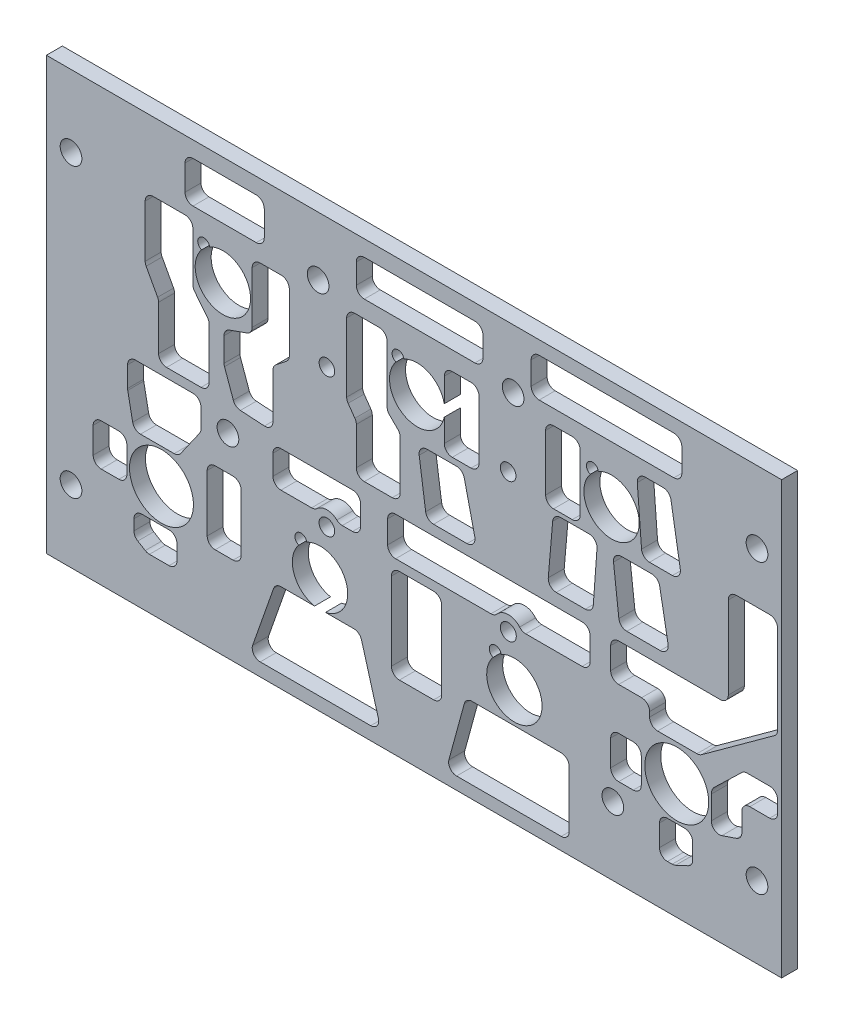
SolidWorks part; units mm, degrees
ref_plane "Front Plane" through (0, 0, 0) normal (0, 0, 1) x (1, 0, 0)
ref_plane "Top Plane" through (0, 0, 0) normal (0, 1, 0) x (1, 0, 0)
ref_plane "Right Plane" through (0, 0, 0) normal (1, 0, 0) x (0, 0, -1)
sketch "Sketch1" plane through (0, 0, 0) normal (0, 0, 1) x (1, 0, 0)
  line L4 (0, 85.725) -> (-146.05, 85.725)
  line L5 (-146.05, 85.725) -> (-146.05, 0)
  line L6 (-146.05, 0) -> (0, 0)
  line L7 (0, 0) -> (0, 85.725)
  line L8 (0, 85.725) -> (-146.05, 85.725)
  line L9 (-146.05, 85.725) -> (-146.05, 0)
  line L10 (-146.05, 0) -> (0, 0)
  line L11 (0, 0) -> (0, 85.725)
  dimension "D1" = 0
extrude "Backplate Body" add sketch "Sketch1" against normal blind 3.175
hole_wizard "#6 Clearance Hole1" positions "Sketch3" profile "Sketch2" hole size "#6" standard "ANSI Inch"
sketch "Sketch3" plane through (0, 0, -3.175) normal (0, 0, -1) x (-1, 0, 0)
  point P0 (4.8895, 71.4375)
  point P3 (53.34, 74.041)
  point P6 (92.075, 74.041)
  point P9 (141.1605, 71.4375)
  point P12 (109.982, 38.735)
  point P15 (141.1605, 14.2875)
  point P18 (33.528, 13.589)
  point P21 (4.8895, 14.2875)
sketch "Sketch2" plane through (-4.8895, 71.4375, -3.175) normal (1, 0, 0) x (0, 1, 0)
  line L0 (0, 0) -> (0, 13.9934)
  line L1 (0, 13.9934) -> (2.1526, 12.7)
  line L2 (2.1526, 12.7) -> (2.1526, 0)
  line L5 (2.1526, 0) -> (0, 0)
  line L10 (0, 13.9934) -> (-2.1526, 12.7) construction
  line L11 (0, -6.35) -> (0, 107.95) construction
  dimension "Hole Dia." = 4.3053
  dimension "Hole Depth" = 12.7
  dimension "Drill Angle" = 118
sketch "Sketch4" plane through (0, 0, -3.175) normal (0, 0, -1) x (-1, 0, 0)
  circle A0 centre (20.828, 22.987) radius 6.35
  circle A1 centre (123.19, 22.987) radius 6.35
  arc A2 (36.4069, 68.9682) -> (38.001, 67.6635) centre (33.782, 64.135) ccw
  arc A3 (75.0149, 68.9682) -> (76.609, 67.6635) centre (72.39, 64.135) ccw
  arc A4 (113.6229, 68.9682) -> (115.217, 67.6635) centre (110.998, 64.135) ccw
  arc A5 (94.3189, 27.8202) -> (95.913, 26.5155) centre (91.694, 22.987) ccw
  arc A6 (55.7109, 27.8202) -> (57.305, 26.5155) centre (53.086, 22.987) ccw
  arc A7 (38.001, 67.6635) -> (36.4069, 68.9682) centre (37.5823, 68.778) ccw
  arc A8 (76.609, 67.6635) -> (75.0149, 68.9682) centre (76.1903, 68.778) ccw
  arc A9 (115.217, 67.6635) -> (113.6229, 68.9682) centre (114.7983, 68.778) ccw
  arc A10 (57.305, 26.5155) -> (55.7109, 27.8202) centre (56.8863, 27.63) ccw
  arc A11 (95.913, 26.5155) -> (94.3189, 27.8202) centre (95.4943, 27.63) ccw
  dimension "D1" = 12.7
  dimension "D2" = 11
  dimension "D3" = 2.3813
extrude "Switch Mount Holes" cut sketch "Sketch4" against normal through all
sketch "Sketch6" plane through (0, 0, -3.175) normal (0, 0, -1) x (-1, 0, 0)
  line L0 (0.7854, 59.7497) -> (0.7854, 42.2627)
  line L1 (1.4397, 40.9784) -> (15.8873, 30.4799)
  line L4 (16.8205, 30.1766) -> (24.6388, 30.1766)
  line L5 (26.2263, 31.7641) -> (26.2263, 32.7329)
  line L6 (27.8138, 34.3204) -> (32.3673, 34.3204)
  line L7 (33.9548, 35.9079) -> (33.9548, 40.2156)
  line L8 (32.3673, 41.8031) -> (12.1743, 41.8031)
  line L9 (10.5868, 43.3906) -> (10.5868, 59.7497)
  line L10 (8.9993, 61.3372) -> (2.3729, 61.3372)
  line L11 (21.4, 75.3506) -> (48.1668, 75.3506)
  line L12 (49.7543, 76.9381) -> (49.7543, 81.4624)
  line L13 (48.1668, 83.0499) -> (21.4, 83.0499)
  line L14 (19.8125, 81.4624) -> (19.8125, 76.9381)
  line L15 (59.3356, 80.9492) -> (59.3356, 76.9381)
  line L16 (60.9231, 75.3506) -> (82.8992, 75.3506)
  line L17 (84.4867, 76.9381) -> (84.4867, 80.9492)
  line L18 (82.8992, 82.5367) -> (60.9231, 82.5367)
  line L19 (28.672, 70.9074) -> (27.8272, 59.8641)
  line L20 (26.2443, 58.3977) -> (21.6898, 58.3977)
  line L21 (20.1244, 60.2489) -> (21.9848, 71.2922)
  line L22 (23.5503, 72.616) -> (27.0892, 72.616)
  line L23 (46.8767, 70.769) -> (46.8767, 59.6575)
  line L24 (45.2892, 58.07) -> (41.5893, 58.07)
  line L25 (40.0018, 59.6575) -> (40.0018, 70.769)
  line L26 (41.5893, 72.3565) -> (45.2892, 72.3565)
  line L27 (38.2576, 57.2789) -> (43.8996, 57.2789)
  line L28 (45.4813, 55.8276) -> (46.355, 45.6783)
  line L29 (44.7734, 43.9546) -> (38.997, 43.9546)
  line L30 (37.4137, 45.4268) -> (36.6743, 55.5761)
  line L31 (24.2194, 55.3227) -> (22.5486, 46.1448)
  line L32 (24.1104, 44.273) -> (30.7553, 44.273)
  line L33 (32.3322, 45.6779) -> (33.3948, 54.8558)
  line L34 (31.8178, 56.6259) -> (25.7812, 56.6259)
  line L35 (61.6963, 71.619) -> (65.4237, 71.619)
  line L36 (67.0112, 70.0315) -> (67.0112, 58.4598)
  line L37 (65.4237, 56.8723) -> (61.6963, 56.8723)
  line L38 (60.1088, 58.4598) -> (60.1088, 70.0315)
  line L39 (78.3684, 70.3657) -> (78.3684, 59.0552)
  line L40 (77.9034, 57.9327) -> (76.2306, 56.2599)
  line L41 (75.7657, 55.1374) -> (75.7657, 45.5421)
  line L42 (77.3532, 43.9546) -> (82.8992, 43.9546)
  line L43 (84.4867, 45.5421) -> (84.4867, 52.9982)
  line L44 (84.774, 53.9091) -> (86.1126, 55.8195)
  line L45 (86.3999, 56.7304) -> (86.3999, 70.3657)
  line L46 (84.8124, 71.9532) -> (79.9559, 71.9532)
  line L47 (64.5881, 55.7521) -> (70.4272, 55.7521)
  line L48 (71.9989, 53.9418) -> (70.7103, 44.8514)
  line L49 (69.1385, 43.4867) -> (62.4983, 43.4867)
  line L50 (60.9512, 45.4299) -> (63.041, 54.5203)
  line L51 (104.3617, 82.5367) -> (116.9306, 82.5367)
  line L52 (118.5181, 80.9492) -> (118.5181, 75.9239)
  line L53 (116.9306, 74.3364) -> (104.3617, 74.3364)
  line L54 (102.7742, 75.9239) -> (102.7742, 80.9492)
  line L55 (116.9515, 70.4508) -> (116.9515, 60.795)
  line L56 (116.6029, 59.8023) -> (114.0887, 56.6647)
  line L57 (113.7401, 55.6721) -> (113.7401, 45.5421)
  line L58 (115.3276, 43.9546) -> (122.1785, 43.9546)
  line L59 (123.766, 45.5421) -> (123.766, 54.3743)
  line L60 (123.9579, 55.131) -> (126.2372, 59.3351)
  line L61 (126.4292, 60.0918) -> (126.4292, 70.4508)
  line L62 (124.8417, 72.0383) -> (118.539, 72.0383)
  line L63 (105.1722, 69.6262) -> (105.1722, 59.351)
  line L64 (106.2241, 57.8565) -> (109.7117, 56.6066)
  line L65 (110.7636, 55.1122) -> (110.7636, 50.368)
  line L66 (110.6706, 49.8324) -> (108.9167, 44.9385)
  line L67 (107.5209, 43.8896) -> (102.7372, 43.5917)
  line L68 (101.051, 45.1761) -> (101.051, 54.0148)
  line L69 (100.4562, 55.2536) -> (98.3918, 56.9078)
  line L70 (97.797, 58.1467) -> (97.797, 69.6262)
  line L71 (99.3845, 71.2137) -> (103.5847, 71.2137)
  line L72 (39.6269, 33.7908) -> (50.842, 33.7908)
  line L73 (78.2665, 35.3783) -> (78.2665, 39.8664)
  line L74 (76.679, 41.4539) -> (39.6269, 41.4539)
  line L75 (38.0394, 39.8664) -> (38.0394, 35.3783)
  line L76 (83.642, 39.7608) -> (83.642, 35.7883)
  line L77 (85.2295, 34.2008) -> (87.2841, 34.2008)
  line L78 (101.051, 35.7883) -> (101.051, 39.7608)
  line L79 (99.4635, 41.3483) -> (85.2295, 41.3483)
  line L80 (115.3458, 40.5393) -> (115.3458, 36.8018)
  line L81 (115.6328, 35.8915) -> (119.3681, 30.5551)
  line L82 (120.6686, 29.8779) -> (127.3572, 29.8779)
  line L83 (128.9152, 31.1612) -> (129.8894, 36.1507)
  line L84 (129.9188, 36.4549) -> (129.9188, 40.5393)
  line L85 (128.3313, 42.1268) -> (116.9333, 42.1268)
  line L86 (0.7854, 30.2344) -> (0.7854, 27.9015)
  line L87 (2.3729, 26.314) -> (6.3156, 26.314)
  line L88 (7.9031, 24.7265) -> (7.9031, 21.0409)
  line L91 (13.9709, 20.0555) -> (13.9709, 24.6575)
  line L92 (13.3361, 26.1523) -> (7.9216, 31.3768)
  line L93 (6.8193, 31.8219) -> (2.3729, 31.8219)
  line L94 (18.5828, 10.0167) -> (21.0703, 8.8579)
  line L95 (21.7407, 8.7095) -> (22.6736, 8.7095)
  line L96 (24.2611, 10.297) -> (24.2611, 14.5475)
  line L97 (22.6736, 16.135) -> (19.2531, 16.135)
  line L98 (17.6656, 14.5475) -> (17.6656, 11.4558)
  line L99 (27.8819, 24.3095) -> (27.8819, 19.1834)
  line L100 (29.4694, 17.5959) -> (32.3673, 17.5959)
  line L101 (33.9548, 19.1834) -> (33.9548, 24.3095)
  line L102 (32.3673, 25.897) -> (29.4694, 25.897)
  line L103 (43.7793, 2.4684) -> (64.5682, 2.4684)
  line L104 (66.0995, 4.4745) -> (63.0373, 15.675)
  line L105 (61.506, 16.8438) -> (43.7793, 16.8438)
  line L106 (42.1918, 15.2563) -> (42.1918, 4.0559)
  line L107 (67.5359, 30.389) -> (67.5359, 14.8805)
  line L108 (69.1234, 13.293) -> (75.9295, 13.293)
  line L109 (77.517, 14.8805) -> (77.517, 30.389)
  line L110 (75.9295, 31.9765) -> (69.1234, 31.9765)
  line L111 (83.4506, 16.4411) -> (80.1004, 4.6154)
  line L112 (81.6278, 2.5952) -> (103.578, 2.5952)
  line L113 (105.0761, 4.708) -> (100.9298, 16.5336)
  line L114 (99.4317, 17.5959) -> (84.978, 17.5959)
  line L115 (114.1111, 30.2647) -> (114.1111, 18.9987)
  line L116 (112.5236, 17.4112) -> (108.9618, 17.4112)
  line L117 (107.3743, 18.9987) -> (107.3743, 30.2647)
  line L118 (108.9618, 31.8522) -> (112.5236, 31.8522)
  line L119 (130.0717, 26.6877) -> (130.0717, 21.5613)
  line L120 (131.6592, 19.9738) -> (135.1785, 19.9738)
  line L121 (136.766, 21.5613) -> (136.766, 26.6877)
  line L122 (135.1785, 28.2752) -> (131.6592, 28.2752)
  line L123 (121.6942, 16.2539) -> (127.0772, 16.2539)
  line L124 (128.6647, 14.6664) -> (128.6647, 12.5851)
  line L125 (127.9016, 11.2285) -> (126.4171, 10.3264)
  line L126 (125.5927, 10.0955) -> (121.6942, 10.0955)
  line L127 (120.1067, 11.683) -> (120.1067, 14.6664)
  line L129 (57.7397, 33.7908) -> (76.679, 33.7908)
  line L130 (93.3749, 34.2008) -> (99.4635, 34.2008)
  line L131 (8.9787, 19.5382) -> (11.8715, 18.5528)
  line L132 (0.0043, 85.727) -> (146.0543, 85.727) construction
  line L133 (0.0043, 85.727) -> (0.0043, 0.002) construction
  arc A0 (121.6942, 10.0955) -> (120.1067, 11.683) centre (121.6942, 11.683) cw
  arc A1 (126.4171, 10.3264) -> (125.5927, 10.0955) centre (125.5927, 11.683) cw
  arc A2 (128.6647, 12.5851) -> (127.9016, 11.2285) centre (127.0772, 12.5851) cw
  arc A3 (127.0772, 16.2539) -> (128.6647, 14.6664) centre (127.0772, 14.6664) cw
  arc A4 (136.766, 26.6877) -> (135.1785, 28.2752) centre (135.1785, 26.6877) ccw
  arc A5 (121.6942, 16.2539) -> (120.1067, 14.6664) centre (121.6942, 14.6664) ccw
  arc A6 (135.1785, 19.9738) -> (136.766, 21.5613) centre (135.1785, 21.5613) ccw
  arc A7 (130.0717, 21.5613) -> (131.6592, 19.9738) centre (131.6592, 21.5613) ccw
  arc A8 (130.0717, 26.6877) -> (131.6592, 28.2752) centre (131.6592, 26.6877) cw
  arc A9 (107.3743, 30.2647) -> (108.9618, 31.8522) centre (108.9618, 30.2647) cw
  arc A10 (108.9618, 17.4112) -> (107.3743, 18.9987) centre (108.9618, 18.9987) cw
  arc A11 (114.1111, 18.9987) -> (112.5236, 17.4112) centre (112.5236, 18.9987) cw
  arc A12 (114.1111, 30.2647) -> (112.5236, 31.8522) centre (112.5236, 30.2647) ccw
  arc A13 (103.578, 2.5952) -> (105.0761, 4.708) centre (103.578, 4.1827) ccw
  arc A14 (100.9298, 16.5336) -> (99.4317, 17.5959) centre (99.4317, 16.0084) ccw
  arc A15 (80.1004, 4.6154) -> (81.6278, 2.5952) centre (81.6278, 4.1827) ccw
  arc A16 (83.4506, 16.4411) -> (84.978, 17.5959) centre (84.978, 16.0084) cw
  arc A17 (77.517, 30.389) -> (75.9295, 31.9765) centre (75.9295, 30.389) ccw
  arc A18 (75.9295, 13.293) -> (77.517, 14.8805) centre (75.9295, 14.8805) ccw
  arc A19 (67.5359, 14.8805) -> (69.1234, 13.293) centre (69.1234, 14.8805) ccw
  arc A20 (43.7793, 16.8438) -> (42.1918, 15.2563) centre (43.7793, 15.2563) ccw
  arc A21 (63.0373, 15.675) -> (61.506, 16.8438) centre (61.506, 15.2563) ccw
  arc A22 (67.5359, 30.389) -> (69.1234, 31.9765) centre (69.1234, 30.389) cw
  arc A23 (64.5682, 2.4684) -> (66.0995, 4.4745) centre (64.5682, 4.0559) ccw
  arc A24 (43.7793, 2.4684) -> (42.1918, 4.0559) centre (43.7793, 4.0559) cw
  arc A25 (32.3673, 17.5959) -> (33.9548, 19.1834) centre (32.3673, 19.1834) ccw
  arc A26 (33.9548, 24.3095) -> (32.3673, 25.897) centre (32.3673, 24.3095) ccw
  arc A27 (27.8819, 19.1834) -> (29.4694, 17.5959) centre (29.4694, 19.1834) ccw
  arc A28 (27.8819, 24.3095) -> (29.4694, 25.897) centre (29.4694, 24.3095) cw
  arc A29 (19.2531, 16.135) -> (17.6656, 14.5475) centre (19.2531, 14.5475) ccw
  arc A30 (24.2611, 14.5475) -> (22.6736, 16.135) centre (22.6736, 14.5475) ccw
  arc A31 (22.6736, 8.7095) -> (24.2611, 10.297) centre (22.6736, 10.297) ccw
  arc A32 (21.0703, 8.8579) -> (21.7407, 8.7095) centre (21.7407, 10.297) ccw
  arc A33 (18.5828, 10.0167) -> (17.6656, 11.4558) centre (19.2531, 11.4558) cw
  arc A34 (7.9216, 31.3768) -> (6.8193, 31.8219) centre (6.8193, 30.2344) ccw
  arc A37 (13.9709, 24.6575) -> (13.3361, 26.1523) centre (11.8938, 24.6575) ccw
  arc A39 (6.3156, 26.314) -> (7.9031, 24.7265) centre (6.3156, 24.7265) cw
  arc A40 (0.7854, 27.9015) -> (2.3729, 26.314) centre (2.3729, 27.9015) ccw
  arc A41 (0.7854, 30.2344) -> (2.3729, 31.8219) centre (2.3729, 30.2344) cw
  arc A42 (129.9188, 40.5393) -> (128.3313, 42.1268) centre (128.3313, 40.5393) ccw
  arc A43 (127.3572, 29.8779) -> (128.9152, 31.1612) centre (127.3572, 31.4654) ccw
  arc A44 (129.8894, 36.1507) -> (129.9188, 36.4549) centre (128.3313, 36.4549) ccw
  arc A45 (119.3681, 30.5551) -> (120.6686, 29.8779) centre (120.6686, 31.4654) ccw
  arc A46 (115.3458, 36.8018) -> (115.6328, 35.8915) centre (116.9333, 36.8018) ccw
  arc A47 (115.3458, 40.5393) -> (116.9333, 42.1268) centre (116.9333, 40.5393) cw
  arc A48 (99.4635, 34.2008) -> (101.051, 35.7883) centre (99.4635, 35.7883) ccw
  arc A49 (101.051, 39.7608) -> (99.4635, 41.3483) centre (99.4635, 39.7608) ccw
  arc A50 (83.642, 35.7883) -> (85.2295, 34.2008) centre (85.2295, 35.7883) ccw
  arc A51 (83.642, 39.7608) -> (85.2295, 41.3483) centre (85.2295, 39.7608) cw
  arc A52 (39.6269, 41.4539) -> (38.0394, 39.8664) centre (39.6269, 39.8664) ccw
  arc A53 (78.2665, 39.8664) -> (76.679, 41.4539) centre (76.679, 39.8664) ccw
  arc A54 (76.679, 33.7908) -> (78.2665, 35.3783) centre (76.679, 35.3783) ccw
  arc A55 (39.6269, 33.7908) -> (38.0394, 35.3783) centre (39.6269, 35.3783) cw
  arc A56 (97.797, 69.6262) -> (99.3845, 71.2137) centre (99.3845, 69.6262) cw
  arc A57 (98.3918, 56.9078) -> (97.797, 58.1467) centre (99.3845, 58.1467) cw
  arc A58 (102.7372, 43.5917) -> (101.051, 45.1761) centre (102.6385, 45.1761) cw
  arc A59 (101.051, 54.0148) -> (100.4562, 55.2536) centre (99.4635, 54.0148) ccw
  arc A60 (110.7636, 50.368) -> (110.6706, 49.8324) centre (109.1761, 50.368) cw
  arc A61 (108.9167, 44.9385) -> (107.5209, 43.8896) centre (107.4222, 45.4741) cw
  arc A62 (109.7117, 56.6066) -> (110.7636, 55.1122) centre (109.1761, 55.1122) cw
  arc A63 (105.1722, 59.351) -> (106.2241, 57.8565) centre (106.7597, 59.351) ccw
  arc A64 (126.4292, 70.4508) -> (124.8417, 72.0383) centre (124.8417, 70.4508) ccw
  arc A65 (126.2372, 59.3351) -> (126.4292, 60.0918) centre (124.8417, 60.0918) ccw
  arc A66 (105.1722, 69.6262) -> (103.5847, 71.2137) centre (103.5847, 69.6262) ccw
  arc A67 (122.1785, 43.9546) -> (123.766, 45.5421) centre (122.1785, 45.5421) ccw
  arc A68 (113.7401, 45.5421) -> (115.3276, 43.9546) centre (115.3276, 45.5421) ccw
  arc A69 (114.0887, 56.6647) -> (113.7401, 55.6721) centre (115.3276, 55.6721) ccw
  arc A70 (123.766, 54.3743) -> (123.9579, 55.131) centre (125.3535, 54.3743) cw
  arc A71 (116.9515, 60.795) -> (116.6029, 59.8023) centre (115.364, 60.795) cw
  arc A72 (116.9515, 70.4508) -> (118.539, 72.0383) centre (118.539, 70.4508) cw
  arc A73 (104.3617, 74.3364) -> (102.7742, 75.9239) centre (104.3617, 75.9239) cw
  arc A74 (118.5181, 75.9239) -> (116.9306, 74.3364) centre (116.9306, 75.9239) cw
  arc A75 (116.9306, 82.5367) -> (118.5181, 80.9492) centre (116.9306, 80.9492) cw
  arc A76 (104.3617, 82.5367) -> (102.7742, 80.9492) centre (104.3617, 80.9492) ccw
  arc A77 (62.4983, 43.4867) -> (60.9512, 45.4299) centre (62.4983, 45.0742) cw
  arc A78 (70.7103, 44.8514) -> (69.1385, 43.4867) centre (69.1385, 45.0742) cw
  arc A79 (70.4272, 55.7521) -> (71.9989, 53.9418) centre (70.4272, 54.1646) cw
  arc A80 (86.3999, 70.3657) -> (84.8124, 71.9532) centre (84.8124, 70.3657) ccw
  arc A81 (64.5881, 55.7521) -> (63.041, 54.5203) centre (64.5881, 54.1646) ccw
  arc A82 (86.1126, 55.8195) -> (86.3999, 56.7304) centre (84.8124, 56.7304) ccw
  arc A83 (82.8992, 43.9546) -> (84.4867, 45.5421) centre (82.8992, 45.5421) ccw
  arc A84 (75.7657, 45.5421) -> (77.3532, 43.9546) centre (77.3532, 45.5421) ccw
  arc A85 (65.4237, 71.619) -> (67.0112, 70.0315) centre (65.4237, 70.0315) cw
  arc A86 (61.6963, 71.619) -> (60.1088, 70.0315) centre (61.6963, 70.0315) ccw
  arc A87 (76.2306, 56.2599) -> (75.7657, 55.1374) centre (77.3532, 55.1374) ccw
  arc A88 (84.4867, 52.9982) -> (84.774, 53.9091) centre (86.0742, 52.9982) cw
  arc A89 (78.3684, 59.0552) -> (77.9034, 57.9327) centre (76.7809, 59.0552) cw
  arc A90 (78.3684, 70.3657) -> (79.9559, 71.9532) centre (79.9559, 70.3657) cw
  arc A91 (61.6963, 56.8723) -> (60.1088, 58.4598) centre (61.6963, 58.4598) cw
  arc A92 (67.0112, 58.4598) -> (65.4237, 56.8723) centre (65.4237, 58.4598) cw
  arc A93 (33.3948, 54.8558) -> (31.8178, 56.6259) centre (31.8178, 55.0384) ccw
  arc A94 (30.7553, 44.273) -> (32.3322, 45.6779) centre (30.7553, 45.8605) ccw
  arc A95 (22.5486, 46.1448) -> (24.1104, 44.273) centre (24.1104, 45.8605) ccw
  arc A96 (24.2194, 55.3227) -> (25.7812, 56.6259) centre (25.7812, 55.0384) cw
  arc A97 (46.355, 45.6783) -> (44.7734, 43.9546) centre (44.7734, 45.5421) cw
  arc A98 (38.997, 43.9546) -> (37.4137, 45.4268) centre (38.997, 45.5421) cw
  arc A99 (43.8996, 57.2789) -> (45.4813, 55.8276) centre (43.8996, 55.6914) cw
  arc A100 (38.2576, 57.2789) -> (36.6743, 55.5761) centre (38.2576, 55.6914) ccw
  arc A101 (40.0018, 70.769) -> (41.5893, 72.3565) centre (41.5893, 70.769) cw
  arc A102 (41.5893, 58.07) -> (40.0018, 59.6575) centre (41.5893, 59.6575) cw
  arc A103 (46.8767, 59.6575) -> (45.2892, 58.07) centre (45.2892, 59.6575) cw
  arc A104 (21.9848, 71.2922) -> (23.5503, 72.616) centre (23.5503, 71.0285) cw
  arc A105 (21.6898, 58.3977) -> (20.1244, 60.2489) centre (21.6898, 59.9852) cw
  arc A106 (46.8767, 70.769) -> (45.2892, 72.3565) centre (45.2892, 70.769) ccw
  arc A107 (27.8272, 59.8641) -> (26.2443, 58.3977) centre (26.2443, 59.9852) cw
  arc A108 (28.672, 70.9074) -> (27.0892, 72.616) centre (27.0892, 71.0285) ccw
  arc A109 (84.4867, 80.9492) -> (82.8992, 82.5367) centre (82.8992, 80.9492) ccw
  arc A110 (59.3356, 76.9381) -> (60.9231, 75.3506) centre (60.9231, 76.9381) ccw
  arc A111 (82.8992, 75.3506) -> (84.4867, 76.9381) centre (82.8992, 76.9381) ccw
  arc A112 (10.5868, 59.7497) -> (8.9993, 61.3372) centre (8.9993, 59.7497) ccw
  arc A113 (12.1743, 41.8031) -> (10.5868, 43.3906) centre (12.1743, 43.3906) cw
  arc A114 (32.3673, 34.3204) -> (33.9548, 35.9079) centre (32.3673, 35.9079) ccw
  arc A115 (33.9548, 40.2156) -> (32.3673, 41.8031) centre (32.3673, 40.2156) ccw
  arc A116 (24.6388, 30.1766) -> (26.2263, 31.7641) centre (24.6388, 31.7641) ccw
  arc A117 (26.2263, 32.7329) -> (27.8138, 34.3204) centre (27.8138, 32.7329) cw
  arc A118 (15.8873, 30.4799) -> (16.8205, 30.1766) centre (16.8205, 31.7641) ccw
  arc A119 (59.3356, 80.9492) -> (60.9231, 82.5367) centre (60.9231, 80.9492) cw
  arc A120 (0.7854, 42.2627) -> (1.4397, 40.9784) centre (2.3729, 42.2627) ccw
  arc A121 (0.7854, 59.7497) -> (2.3729, 61.3372) centre (2.3729, 59.7497) cw
  arc A122 (49.7543, 81.4624) -> (48.1668, 83.0499) centre (48.1668, 81.4624) ccw
  arc A123 (48.1668, 75.3506) -> (49.7543, 76.9381) centre (48.1668, 76.9381) ccw
  arc A124 (19.8125, 76.9381) -> (21.4, 75.3506) centre (21.4, 76.9381) ccw
  arc A125 (21.4, 83.0499) -> (19.8125, 81.4624) centre (21.4, 81.4624) ccw
  arc A126 (56.5338, 34.3459) -> (52.048, 34.3459) centre (54.2909, 32.4258) ccw
  arc A127 (50.842, 33.7908) -> (52.048, 34.3459) centre (50.842, 35.3783) ccw
  arc A128 (57.7397, 33.7908) -> (56.5338, 34.3459) centre (57.7397, 35.3783) cw
  arc A129 (92.3069, 34.6138) -> (88.3521, 34.6138) centre (90.3295, 32.439) ccw
  arc A130 (92.3069, 34.6138) -> (93.3749, 34.2008) centre (93.3749, 35.7883) ccw
  arc A131 (88.3521, 34.6138) -> (87.2841, 34.2008) centre (87.2841, 35.7883) cw
  arc A132 (13.9709, 20.0555) -> (11.8715, 18.5528) centre (12.3834, 20.0555) cw
  arc A133 (7.9031, 21.0409) -> (8.9787, 19.5382) centre (9.4906, 21.0409) ccw
  circle A134 centre (90.3252, 59.937) radius 1.55
  circle A135 centre (54.3252, 59.937) radius 1.55
  circle A136 centre (90.3295, 32.439) radius 1.5548
  circle A137 centre (54.2909, 32.4258) radius 1.5861
  point P244 (101.051, 43.4867)
  point P347 (84.4867, 82.5367)
  point P370 (0.7854, 41.4539)
  point P394 (92.6823, 34.2008)
  dimension "D1" = 1.5875
  dimension "D2" = 1.5875
  dimension "D3" = 1.5875
  dimension "D4" = 1.5875
  dimension "D5" = 1.5875
extrude "Backlighting LED Holes" cut sketch "Sketch6" against normal through all
